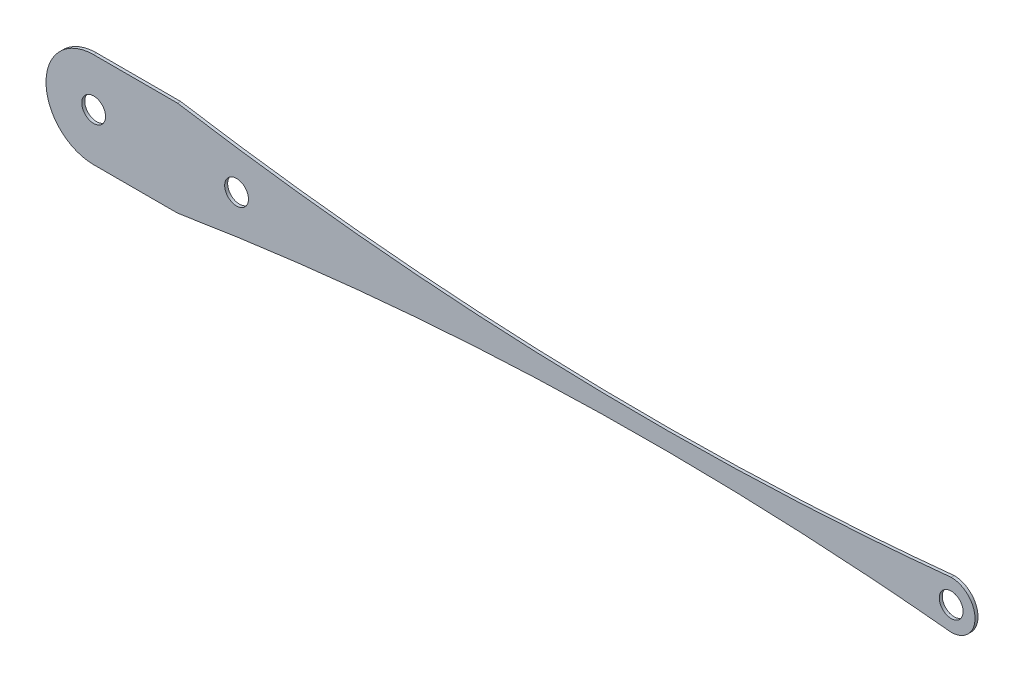
SolidWorks part; units mm, degrees
ref_plane "Front Plane" through (0, 0, 0) normal (0, 0, 1) x (1, 0, 0)
ref_plane "Top Plane" through (0, 0, 0) normal (0, 1, 0) x (1, 0, 0)
ref_plane "Right Plane" through (0, 0, 0) normal (1, 0, 0) x (0, 0, -1)
sketch "Sketch4" plane through (0, 0, 0) normal (0, 0, 1) x (1, 0, 0)
  line L0 (0, 0) -> (457.2, 0) construction
  line L1 (0, 25.4) -> (44.7423, 25.4)
  line L2 (0, -25.4) -> (44.7423, -25.4)
  arc A0 (0, 25.4) -> (0, -25.4) centre (0, 0) ccw
  circle A2 centre (0, 0) radius 6.35
  circle A3 centre (76.2, 0) radius 6.35
  circle A4 centre (457.2, 0) radius 6.35
  arc A5 (457.2, -12.7) -> (457.2, 12.7) centre (457.2, 0) ccw
  arc A6 (44.7423, 25.4) -> (52.6769, 24.1289) centre (44.7423, 0) cw
  arc A7 (52.6769, -24.1289) -> (44.7423, -25.4) centre (44.7423, 0) cw
  spline S0 degree 2 poles (44.7423, 25.4) (249.9499, -8.0007) (457.2, 12.7) knots 0 0 0 1 1 1
  spline S1 degree 2 poles (44.7423, -25.4) (249.9499, 8.0007) (457.2, -12.7) knots 0 0 0 1 1 1
  point P3 (228.6, 0)
  dimension "D3" = 12.7
  dimension "D4" = 12.7
  dimension "D5" = 25.4
  dimension "D1" = 50.8
  dimension "D2" = 457.2
  dimension "D6" = 19.05
  dimension "D7" = 19.05
  dimension "D8" = 76.2
extrude "Boss-Extrude2" add sketch "Sketch4" along normal blind 1.6002 contours L2 S1 A5 S0 L1 A0 A2 A3 A4 region at (158.0374, 0, 0)
